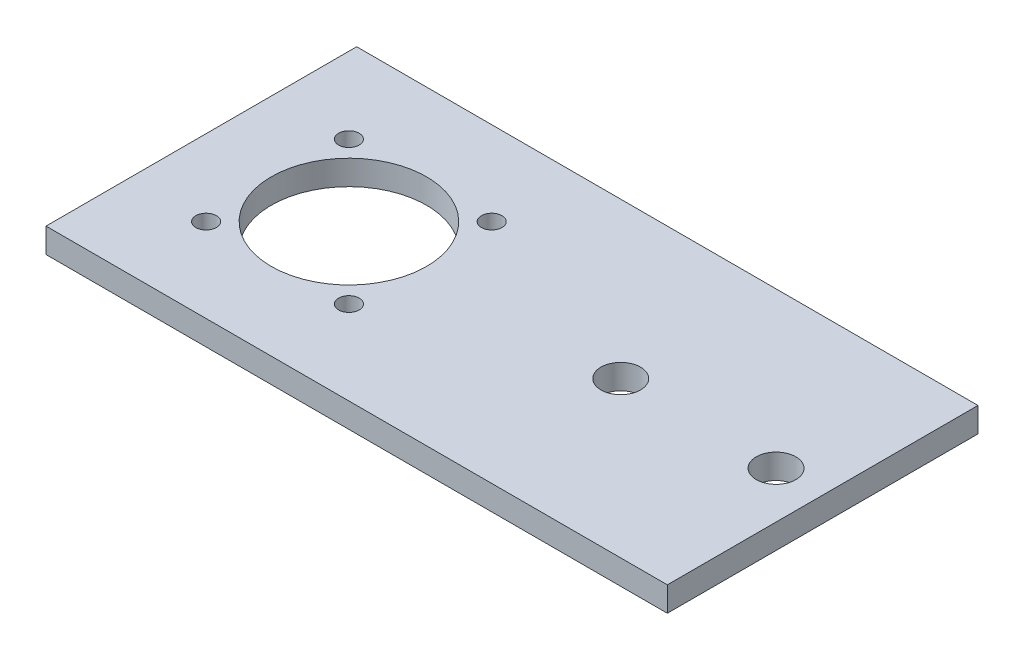
SolidWorks part; units mm, degrees
ref_plane "Front Plane" through (0, 0, 0) normal (0, 0, 1) x (1, 0, 0)
ref_plane "Top Plane" through (0, 0, 0) normal (0, 1, 0) x (1, 0, 0)
ref_plane "Right Plane" through (0, 0, 0) normal (1, 0, 0) x (0, 0, -1)
sketch "Sketch1" plane through (0, 0, 0) normal (0, 1, 0) x (1, 0, 0)
  line L1 (0, 0) -> (80, 0)
  line L2 (0, 0) -> (0, 40)
  line L3 (0, 40) -> (80, 40)
  line L4 (80, 0) -> (80, 40)
  line L5 (31.557, 23.3646) -> (22.3646, 32.557) construction
  line L6 (22.3646, 32.557) -> (9.8076, 29.1924) construction
  line L7 (9.8076, 29.1924) -> (6.443, 16.6354) construction
  line L8 (6.443, 16.6354) -> (15.6354, 7.443) construction
  line L9 (15.6354, 7.443) -> (28.1924, 10.8076) construction
  line L10 (28.1924, 10.8076) -> (31.557, 23.3646) construction
  circle A0 centre (54, 20) radius 2.55
  circle A1 centre (74, 20) radius 2.55
  circle A2 centre (19, 20) radius 11.2583 construction
  circle A3 centre (19, 20) radius 10
  circle A4 centre (28.1924, 10.8076) radius 1.325
  circle A5 centre (19, 20) radius 11.2583 construction
  circle A6 centre (9.8076, 10.8076) radius 1.325
  circle A7 centre (19, 20) radius 11.2583 construction
  circle A8 centre (9.8076, 29.1924) radius 1.325
  circle A9 centre (19, 20) radius 11.2583 construction
  circle A10 centre (28.1924, 29.1924) radius 1.325
  point P10 (19, 7)
  point P19 (0, 0)
  point P20 (0, 20)
  point P21 (0, 0)
  point P32 (19.3439, 20)
  point P33 (6, 20)
  point P34 (28.1984, 10.8137)
  point P38 (19, 20)
  dimension "D3" = 5.1
  dimension "D4" = 20
  dimension "D7" = 20
  dimension "D9" = 2.65
  dimension "D1" = 40
  dimension "D2" = 80
  dimension "D5" = 6
  dimension "D6" = 15
  dimension "D8" = 26
  dimension "D11" = 19
  dimension "D10" = 4
extrude "Boss-Extrude1" add sketch "Sketch1" along normal blind 3.175
